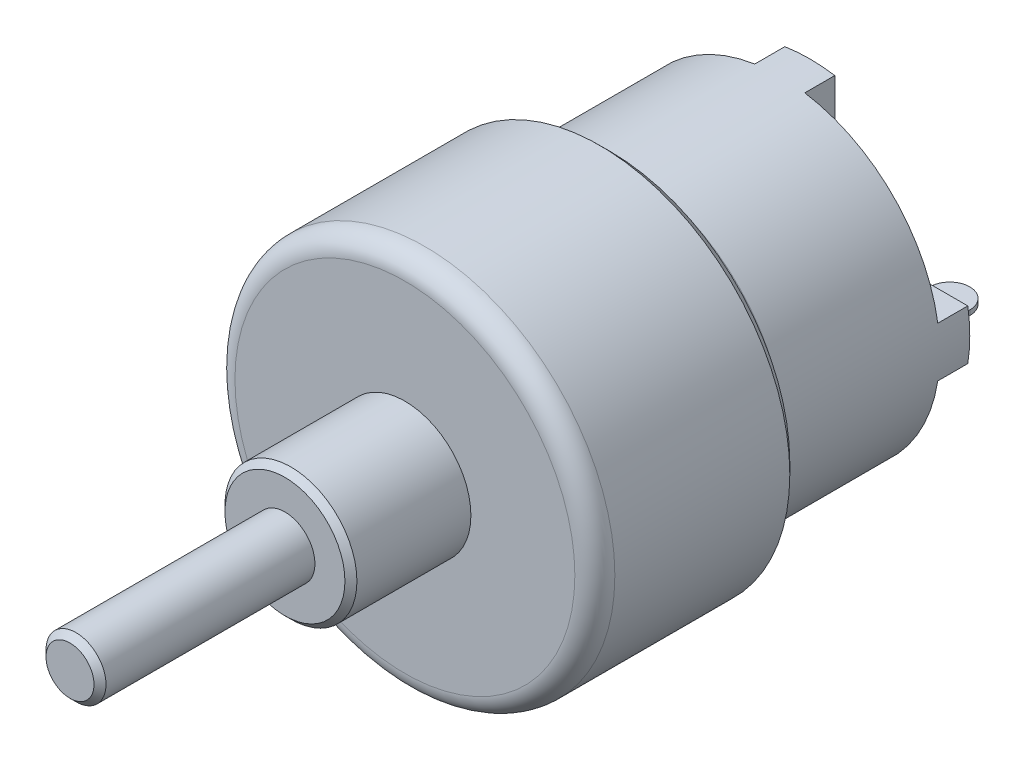
SolidWorks part; units mm, degrees
ref_plane "Front" through (0, 0, 0) normal (0, 0, 1) x (1, 0, 0)
ref_plane "Top" through (0, 0, 0) normal (0, 1, 0) x (1, 0, 0)
ref_plane "Right" through (0, 0, 0) normal (1, 0, 0) x (0, 0, -1)
sketch "Sketch1" plane through (0, 0, 0) normal (0, 0, 1) x (1, 0, 0)
  circle A0 centre (0, 0) radius 16
  dimension "D1" = 32
extrude "Boss-Extrude1" add sketch "Sketch1" along normal blind 17
fillet "Fillet1" radius 1.5 1 edges at (16, 0, 17)
sketch "Sketch3" plane through (0, 0, 0) normal (0, 0, -1) x (-1, 0, 0)
  line L0 (-2.5, 15.8035) -> (-2.5, -15.8035)
  line L1 (2.5, 15.8035) -> (2.5, -15.8035)
  line L2 (0, 0) -> (0, -50000) construction
  circle A0 centre (0, 0) radius 16 construction
  arc A1 (2.5, 15.8035) -> (-2.5, 15.8035) centre (0, 0) ccw
  arc A2 (-2.5, -15.8035) -> (2.5, -15.8035) centre (0, 0) ccw
  dimension "D1" = 5
extrude "Boss-Extrude2" add sketch "Sketch3" along normal blind 3
pattern_circular "CirPattern1" count 4 over 360 about axis through (0, 0, 0) along (0, 0, 1) of "Boss-Extrude2"
fillet "Fillet2" radius 1.5 4 edges at (2.5, 2.5, -1.5) (2.5, -2.5, -1.5) (-2.5, -2.5, -1.5) (-2.5, 2.5, -1.5)
sketch "Sketch5" plane through (0, 0, -3) normal (0, 0, -1) x (-1, 0, 0)
  circle A0 centre (0, 0) radius 3
  dimension "D1" = 6
extrude "Boss-Extrude3" add sketch "Sketch5" along normal blind 3
fillet "Fillet3" radius 0.5 1 edges at (-3, 0, -6)
sketch "Sketch6" plane through (0, 0, 17) normal (0, 0, 1) x (1, 0, 0)
  circle A0 centre (0, 0) radius 19
  dimension "D1" = 38
extrude "Boss-Extrude4" add sketch "Sketch6" along normal blind 20.5
chamfer "Chamfer1" distance 1 angle 45 1 edges at (19, 0, 17)
sketch "Sketch7" plane through (0, 0, -3) normal (0, 0, -1) x (-1, 0, 0)
  line L0 (0, 0) -> (-50000, 0) construction
  line L1 (0, 0) -> (0, -50000) construction
  line L2 (14, -0.25) -> (10, -0.25)
  line L3 (14, -0.25) -> (14, 0.25)
  line L4 (14, 0.25) -> (10, 0.25)
  line L5 (10, -0.25) -> (10, 0.25)
  line L6 (-10, -0.25) -> (-14, -0.25)
  line L7 (-10, -0.25) -> (-10, 0.25)
  line L8 (-10, 0.25) -> (-14, 0.25)
  line L9 (-14, -0.25) -> (-14, 0.25)
  dimension "D1" = 0.5
  dimension "D2" = 0.5
  dimension "D3" = 20
  dimension "D4" = 4
extrude "Boss-Extrude5" add sketch "Sketch7" along normal blind 4
fillet "Fillet4" radius 2 4 edges at (14, 0, -7) (10, 0, -7) (-10, 0, -7) (-14, 0, -7)
fillet "Fillet5" radius 2 1 edges at (19, 0, 37.5)
sketch "Sketch8" plane through (0, 0, 37.5) normal (0, 0, 1) x (1, 0, 0)
  circle A0 centre (0, 0) radius 6.6
  dimension "D1" = 13.2
extrude "Boss-Extrude6" add sketch "Sketch8" along normal blind 12
sketch "Sketch9" plane through (0, 0, 49.5) normal (0, 0, 1) x (1, 0, 0)
  circle A0 centre (0, 0) radius 3
  dimension "D1" = 6
extrude "Boss-Extrude7" add sketch "Sketch9" along normal blind 21.5
chamfer "Chamfer2" distance 0.6 angle 45 1 edges at (3, 0, 71)
chamfer "Chamfer3" distance 0.6 angle 45 1 edges at (6.6, 0, 49.5)
